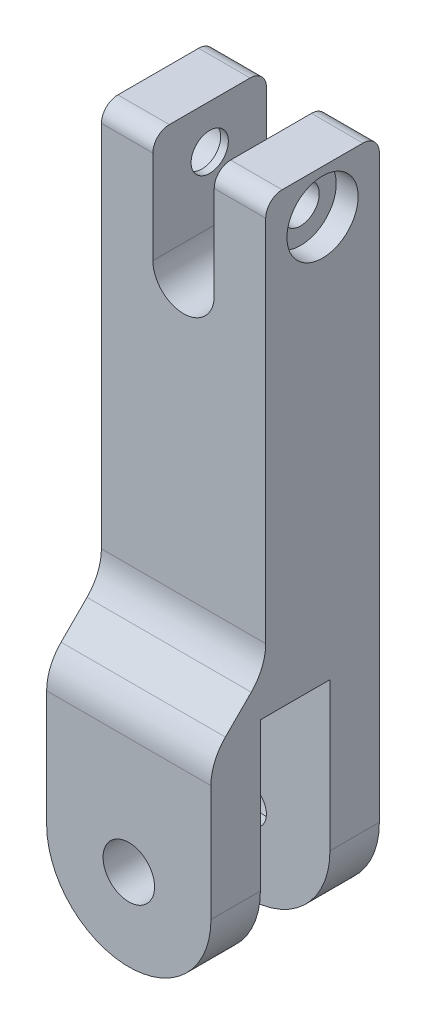
SolidWorks part; units mm, degrees
ref_plane "Front Plane" through (0, 0, 0) normal (0, 0, 1) x (1, 0, 0)
ref_plane "Top Plane" through (0, 0, 0) normal (0, 1, 0) x (1, 0, 0)
ref_plane "Right Plane" through (0, 0, 0) normal (1, 0, 0) x (0, 0, -1)
sketch "Sketch1" plane through (0, 0, 0) normal (0, 0, 1) x (1, 0, 0)
  line L6 (-7.5, 0) -> (-7.5, 54.45)
  line L7 (-7.5, 54.45) -> (7.5, 54.45)
  line L8 (7.5, 0) -> (7.5, 54.45)
  arc A0 (-7.5, 0) -> (7.5, 0) centre (0, 0) ccw
  dimension "D2" = 7.5
  dimension "D1" = 54.45
extrude "Boss-Extrude1" add sketch "Sketch1" along normal blind 15.375
sketch "Sketch2" plane through (7.5, 0, 0) normal (1, 0, 0) x (0, 0, -1)
  line L1 (-15.375, 54.45) -> (-10.375, 54.45)
  line L2 (-15.375, 54.45) -> (-15.375, 17.45)
  line L3 (-15.375, 17.45) -> (-10.375, 17.45)
  line L4 (-10.375, 54.45) -> (-10.375, 17.45)
  dimension "D1" = 5
  dimension "D2" = 37
extrude "Cut-Extrude1" cut sketch "Sketch2" against normal through all
sketch "Sketch3" plane through (7.5, 0, 0) normal (1, 0, 0) x (0, 0, -1)
  line L0 (-15.375, -7.5) -> (0, -7.5) construction
  line L1 (-4.5125, 3.03) -> (-10.8625, 3.03)
  line L2 (-4.5125, 3.03) -> (-4.5125, -7.5)
  line L3 (-4.5125, -7.5) -> (-10.8625, -7.5)
  line L4 (-10.8625, 3.03) -> (-10.8625, -7.5)
  line L5 (-15.375, 0) -> (0, 0) construction
  point P8 (-7.6875, 0)
  point P9 (-7.6875, 3.03)
  dimension "D1" = 6.35
  dimension "D2" = 10.53
extrude "Cut-Extrude2" cut sketch "Sketch3" against normal through all
sketch "Sketch4" plane through (0, 0, 0) normal (0, 0, -1) x (-1, 0, 0)
  line L0 (-7.5, 54.45) -> (7.5, 54.45) construction
  line L1 (-2.8, 54.45) -> (2.8, 54.45)
  line L2 (-2.8, 54.45) -> (-2.8, 44.45)
  line L4 (2.8, 54.45) -> (2.8, 44.45)
  arc A0 (-2.8, 44.45) -> (2.8, 44.45) centre (0, 44.45) ccw
  point P9 (0, 54.45)
  dimension "D2" = 2.8
  dimension "D1" = 10
extrude "Cut-Extrude3" cut sketch "Sketch4" against normal through all
sketch "Sketch5" plane through (0, 0, 15.375) normal (0, 0, 1) x (1, 0, 0)
  circle A0 centre (0, 0) radius 1.7
  circle A1 centre (0, 0) radius 2.35
  dimension "D1" = 3.4
  dimension "D2" = 4.7
extrude "Cut-Extrude4" cut sketch "Sketch5" against normal up to surface (4.5125 mm away) contours A0 region at (0, 0, 15.375) up to face at (0, -0.36, 10.8625)
extrude "Cut-Extrude6" cut sketch "Sketch5<3>" against normal blind 4
sketch "Sketch5<3>" plane through (0, 0, 15.375) normal (0, 0, 1) x (1, 0, 0) same geometry as "Sketch5"
hole_wizard "CBORE for M3 SHCS1" positions "Sketch7" profile "Sketch8" counterbore size "M3" standard "ANSI Metric" end condition up to next
sketch "Sketch7" plane through (0, 0, 0) normal (0, 0, -1) x (-1, 0, 0)
  point P0 (0, 0)
sketch "Sketch8" plane through (0, 0, 0) normal (1, 0, 0) x (0, 1, 0)
  line L0 (0, 0) -> (0, 4.5125)
  line L1 (0, 4.5125) -> (1.7, 4.5125)
  line L3 (1.7, 4.5125) -> (1.7, 3)
  line L4 (1.7, 3) -> (3.25, 3)
  line L5 (3.25, 3) -> (3.25, 0)
  line L7 (3.25, 0) -> (0, 0)
  line L11 (0, -6.35) -> (0, 107.95) construction
  dimension "Thru Hole Dia." = 3.4
  dimension "Thru Hole Depth" = 4.5125
  dimension "C'Bore Dia." = 6.5
  dimension "C'Bore Depth" = 3
sketch "Sketch6" plane through (7.5, 0, 0) normal (1, 0, 0) x (0, 0, -1)
  line L0 (-10.375, 54.45) -> (0, 54.45) construction
  circle A1 centre (-5.1875, 50.45) radius 2.35
  circle A2 centre (-5.1875, 50.45) radius 1.7
  point P5 (-5.1875, 54.45)
  dimension "D2" = 3.4
  dimension "D3" = 4.7
  dimension "D1" = 4
draft "Draft1" type of draft neutral plane draft angle 45 faces to draft 1 face at (0, 17.45, 12.875) neutral plane through (-7.5, 54.45, 10.375) neutral plane normal (0, 0, 1) parameters "D1"=45
draft "Draft2" type of draft neutral plane draft angle 35 faces to draft 1 face at (0, 3.03, 7.6875) neutral plane through (-7.5, 0, 15.375) neutral plane normal (-1, 0, 0) reverse direction yes parameters "D1"=35
fillet "Fillet1" radius 1.5 4 edges at (-5.15, 54.45, 10.375) (-5.15, 54.45, 0) (5.15, 54.45, 0) (5.15, 54.45, 10.375)
fillet "Fillet2" radius 4.5 2 edges at (0, 12.45, 15.375) (0, 17.45, 10.375)
extrude "Cut-Extrude7" cut sketch "Sketch6" along normal blind 4 from surface contours A1 starting at face at (-7.5, 20.0915, 8.4554)
hole_wizard "CBORE for M3 SHCS2" positions "Sketch9" profile "Sketch10" counterbore size "M3" standard "ANSI Metric" end condition up to next
sketch "Sketch9" plane through (7.5, 0, 0) normal (1, 0, 0) x (0, 0, -1)
  circle A0 centre (-5.1875, 50.45) radius 2.35 construction
  point P0 (-5.1875, 50.45)
  point P3 (0, 0)
sketch "Sketch10" plane through (7.5, 50.45, 5.1875) normal (0, 1, 0) x (0, 0, -1)
  line L0 (0, 0) -> (0, 4.7)
  line L1 (0, 4.7) -> (1.7, 4.7)
  line L3 (1.7, 4.7) -> (1.7, 2)
  line L4 (1.7, 2) -> (3.25, 2)
  line L5 (3.25, 2) -> (3.25, 0)
  line L7 (3.25, 0) -> (0, 0)
  line L11 (0, -6.35) -> (0, 107.95) construction
  dimension "Thru Hole Dia." = 3.4
  dimension "Thru Hole Depth" = 4.7
  dimension "C'Bore Dia." = 6.5
  dimension "C'Bore Depth" = 2
extrude "Cut-Extrude8" cut sketch "Sketch6<4>" against normal through all contours A2 region at (7.5, 50.45, 5.1875)
sketch "Sketch6<4>" plane through (7.5, 0, 0) normal (1, 0, 0) x (0, 0, -1) same geometry as "Sketch6"
